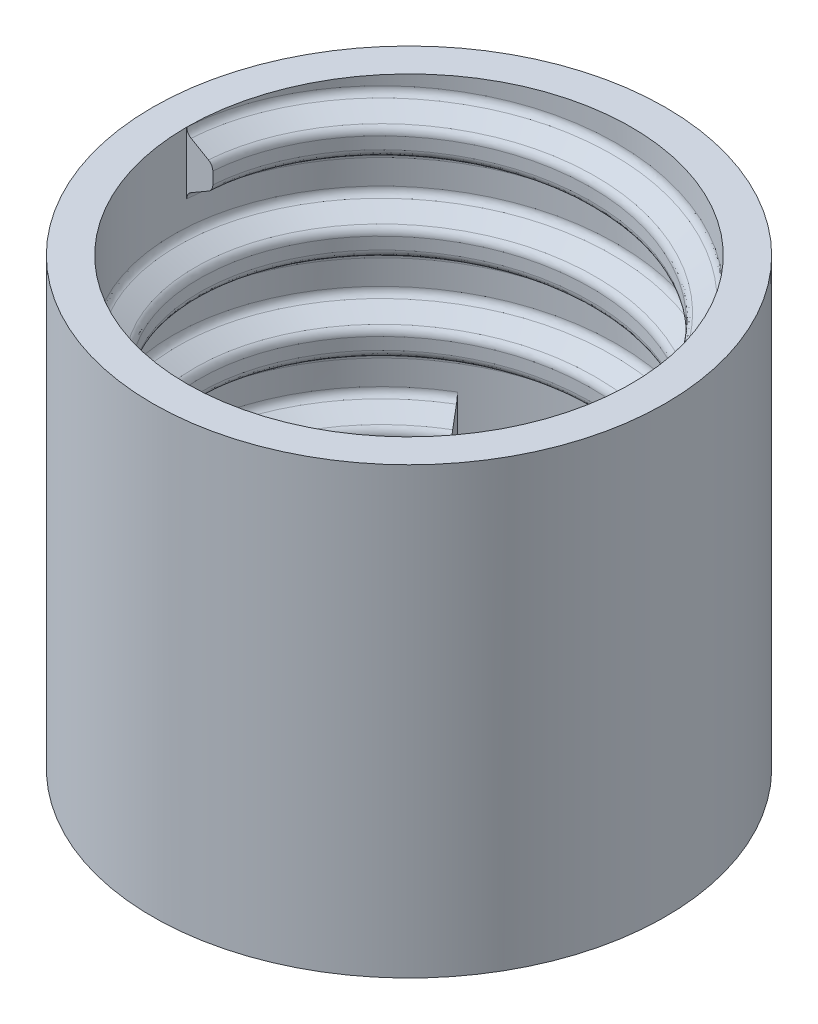
SolidWorks part; units mm, degrees
ref_plane "Front Plane" through (0, 0, 0) normal (0, 0, 1) x (1, 0, 0)
ref_plane "Top Plane" through (0, 0, 0) normal (0, 1, 0) x (1, 0, 0)
ref_plane "Right Plane" through (0, 0, 0) normal (1, 0, 0) x (0, 0, -1)
sketch "Sketch1" plane through (0, 0, 0) normal (0, 1, 0) x (1, 0, 0)
  circle A0 centre (0, 0) radius 15
extrude "Boss-Extrude1" add sketch "Sketch1" along normal blind 20 contours A0
sketch "Sketch2" plane through (0, 20, 0) normal (0, 1, 0) x (1, 0, 0)
  circle A0 centre (0, 0) radius 13
sketch "Sketch10" plane through (0, 20, 0) normal (0, 1, 0) x (1, 0, 0)
  circle A0 centre (0, 0) radius 13
extrude "Cut-Extrude2" cut sketch "Sketch10" against normal blind 20
thread "Thread1" pitch 5.08 method extrude profile "Thread Profile2" start angle 0, offset 0, length 16, pitch 5.08, diameter 26
ref_plane "Plane2" through (-13, 20, 0) normal (0, 0, -1) x (1, 0, 0)
sketch "Thread Profile2" plane through (-13, 20, 0) normal (0, 0, -1) x (1, 0, 0)
  line L0 (0, 0) -> (0, 5.08) construction
  line L1 (0, 0) -> (0, 3.6346)
  line L2 (0.508, 3.6346) -> (1.524, 3.6346) construction
  line L3 (1.524, 2.1681) -> (1.524, 1.4665)
  line L4 (1.27, 2.6081) -> (0.254, 3.1946)
  line L5 (1.27, 1.0265) -> (0.254, 0.4399)
  line L6 (0.508, 0) -> (1.524, 0) construction
  arc A0 (0.254, 3.1946) -> (0, 3.6346) centre (0.508, 3.6346) cw
  arc A1 (0.254, 0.4399) -> (0, 0) centre (0.508, 0) ccw
  arc A2 (1.524, 1.4665) -> (1.27, 1.0265) centre (1.016, 1.4665) cw
  arc A3 (1.524, 2.1681) -> (1.27, 2.6081) centre (1.016, 2.1681) ccw
  point P10 (1.524, 2.4614)
  point P17 (1.524, 1.1732)
  point P18 (0, 3.3413)
  point P19 (0, 0.2933)
  point P20 (0, 0)
  dimension "RootFillet1" = 0.508
  dimension "RootFillet2" = 0.508
  dimension "CrestFillet2" = 0.508
  dimension "CrestFillet1" = 0.508
  dimension "Pitch" = 5.08
  dimension "Angle1" = 30
  dimension "Angle2" = 30
  dimension "a" = 3.048
  dimension "b" = 1.524
  dimension "c" = 1.2882
sketch "Sketch19" plane through (0, 0, 0) normal (0, -1, 0) x (-1, 0, 0)
  circle A0 centre (0, 0) radius 13
  circle A1 centre (0, 0) radius 6.5
sketch "Sketch20" plane through (0, 0, 0) normal (0, -1, 0) x (1, 0, 0)
  circle A0 centre (0, 0) radius 15
extrude "Boss-Extrude3" add sketch "Sketch20" along normal blind 6
extrude "Cut-Extrude3" cut sketch "Sketch19" along normal blind 1.5 contours A1
sketch "Sketch47" plane through (0, -1.5, 0) normal (0, 1, 0) x (1, 0, 0)
  circle A0 centre (0, 0) radius 0.5
extrude "Cut-Extrude10" cut sketch "Sketch47" against normal blind 4.5
sketch "Sketch49" plane through (0, -1.5, 0) normal (0, 1, 0) x (1, 0, 0)
  circle A0 centre (0, 0) radius 0.5
  circle A2 centre (1.67, 0) radius 0.5
sketch "Sketch50" plane through (0, -1.5, 0) normal (0, 1, 0) x (1, 0, 0)
  circle A0 centre (3.33, 0) radius 0.5
sketch "Sketch51" plane through (0, -1.5, 0) normal (0, 1, 0) x (1, 0, 0)
  circle A0 centre (5, 0) radius 0.5
extrude "Cut-Extrude13" cut sketch "Sketch49" against normal blind 4.5
extrude "Cut-Extrude14" cut sketch "Sketch50" against normal blind 4.5
extrude "Cut-Extrude15" cut sketch "Sketch51" against normal blind 4.5
pattern_circular "CirPattern1" count 18 over 360 about axis through (0, -1.5, 0) along (0, 1, 0) of "Cut-Extrude15"
pattern_circular "CirPattern2" count 12 over 360 about axis through (0, -1.5, 0) along (0, 1, 0) of "Cut-Extrude14"
pattern_circular "CirPattern3" count 6 over 360 about axis through (0, -1.5, 0) along (0, 1, 0) of "Cut-Extrude13"
sketch "Sketch52" plane through (0, -6, 0) normal (0, -1, 0) x (-1, 0, 0)
  circle A0 centre (0, 0) radius 15
